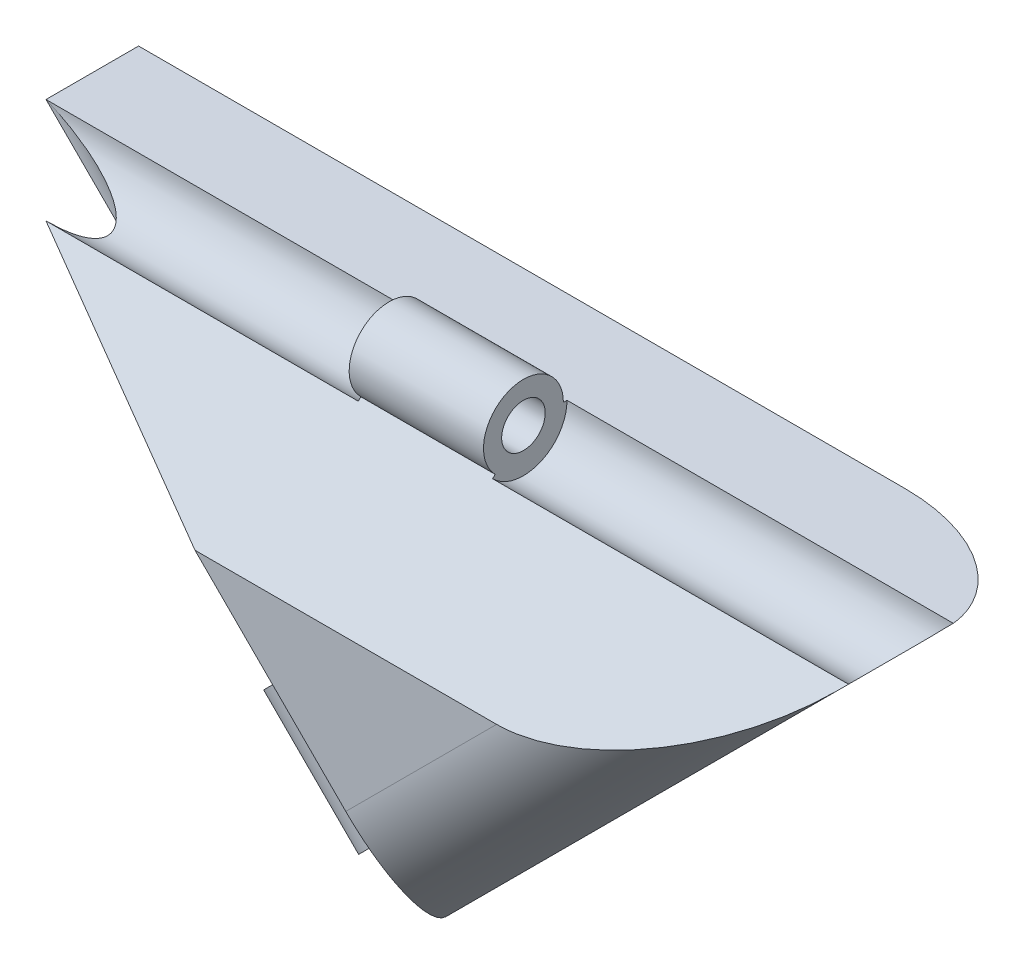
SolidWorks part; units mm, degrees
ref_plane "Front Plane" through (0, 0, 0) normal (1, 0, 0) x (0, 1, 0)
ref_plane "Top Plane" through (0, 0, 0) normal (0, 0, 1) x (0, 1, 0)
ref_plane "Right Plane" through (0, 0, 0) normal (0, 1, 0) x (-1, 0, 0)
sketch "Sketch1" plane through (0, 0, 0) normal (0, 0, 1) x (0, 1, 0)
  line L9 (8.3333, 25) -> (8.3333, -25)
  line L10 (-16.6667, 0) -> (8.3333, -25)
  line L11 (-16.6667, 0) -> (8.3333, 25)
  line L12 (-4.1667, 12.5) -> (8.3333, -25) construction
  line L13 (8.3333, 25) -> (-4.1667, -12.5) construction
  point P1 (0, 0)
  dimension "D1" = 50
  dimension "D2" = 90
extrude "Boss-Extrude1" add sketch "Sketch1" along normal blind 15
sketch "Sketch2" plane through (0, 0, 0) normal (1, 0, 0) x (0, 1, 0)
  line L0 (0.8333, 15) -> (8.3333, 7.5)
  line L1 (8.3333, 15) -> (8.3333, 0) construction
  line L2 (8.3333, 7.5) -> (8.3333, 15)
  line L3 (8.3333, 15) -> (0.8333, 15)
  line L4 (-16.6667, 15) -> (8.3333, 15) construction
  line L5 (8.3333, 5.1) -> (8.3333, 5.3)
  circle A0 centre (8.3333, 7.5) radius 1.2
  circle A1 centre (8.3333, 7.5) radius 2.4
  circle A2 centre (8.3333, 7.5) radius 2.2
  dimension "D2" = 2.4
  dimension "D3" = 0.2
  dimension "D4" = 1
  dimension "D1" = 7.5
extrude "Cut-Extrude1" cut sketch "Sketch2" against normal through all both and the other way through all contours A1 L2 L3 L0 | A2 L2 A1 L0 | L2 A2 L0 A0 | L0 A2 L2 A0 | L0 A0 L2 | L2 A0 L0 | A1 region at (0, 5.6669, 12.8113) region at (0, 7.4751, 9.572) region at (0, 7.6811, 9.0747) region at (0, 7.0873, 8.6581) region at (0, 8.035, 8.2203) region at (0, 8.376, 7.3971)
extrude "Boss-Extrude2" add sketch "Sketch2<5>" along normal blind 3.7 and the other way blind 3.7 contours A2 L0 A1 L5 | A2 L2 A0 L0 | L2 A2 L0 A0 region at (0, 6.6734, 9.0928) region at (0, 7.6811, 9.0747) region at (0, 7.0873, 8.6581)
sketch "Sketch2<5>" plane through (0, 0, 0) normal (1, 0, 0) x (0, 1, 0) same geometry as "Sketch2"
sketch "Sketch4" plane through (8.3333, -8.3333, 0) normal (0.7071, -0.7071, 0) x (0.7071, 0.7071, 0)
  line L0 (-11.7851, 7.5) -> (-4.2851, 15)
  line L1 (-11.7851, 15) -> (-11.7851, 0) construction
  line L2 (-11.7851, 15) -> (12.9636, 15) construction
  line L3 (-4.2851, 15) -> (-11.7851, 15)
  line L4 (-11.7851, 15) -> (-11.7851, 7.5)
  line L5 (-11.7851, 5.1) -> (-11.7851, 7.5)
  circle A0 centre (-11.7851, 7.5) radius 1.2
  circle A1 centre (-11.7851, 7.5) radius 2.2
  circle A2 centre (-11.7851, 7.5) radius 2.4
  line M6 (12.9636, 15) -> (-11.7851, 15)
  line M7 (-11.7851, 15) -> (-11.7851, 0)
  dimension "D1" = 2.4
  dimension "D2" = 1
  dimension "D3" = 0.2
extrude "Cut-Extrude2" cut sketch "Sketch4" against normal through all contours L0 A0 L4 | A0 L0 M7 | L5 A1 L0 A0 | L0 A1 L4 A0 | L0 A2 L4 A1 | A2 L0 M6 M7 | A2 region at (0.211, -16.4557, 8.2203) region at (0.4098, -16.2568, 7.2599) region at (0.4612, -16.2055, 9.0747) region at (0.896, -15.7706, 6.9751) region at (0.6069, -16.0598, 9.572) region at (1.8855, -14.7812, 12.8113)
extrude "Boss-Extrude3" add sketch "Sketch4<3>" against normal blind 7.4 from offset 3.8 contours A2 L0 A1 M7 | L5 A1 L0 A0 | L4 A1 L5 A0 | L0 A1 L4 A0 region at (0.4612, -16.2055, 9.0747) region at (0.896, -15.7706, 6.9751) region at (-0.8833, -17.55, 7.5) region at (1.1737, -15.4929, 9.0928) offset against normal yes
sketch "Sketch4<3>" plane through (8.3333, -8.3333, 0) normal (0.7071, -0.7071, 0) x (0.7071, 0.7071, 0) same geometry as "Sketch4"
ref_plane "Plane1" through (0, 0, 2.65) normal (0, 0, 1) x (0, 1, 0)
fillet "Fillet1" radius 5.5 1 edges at (12.5, -4.1667, 0)
fillet "Fillet2" radius 5.5 1 edges at (11.4017, -5.265, 15)
